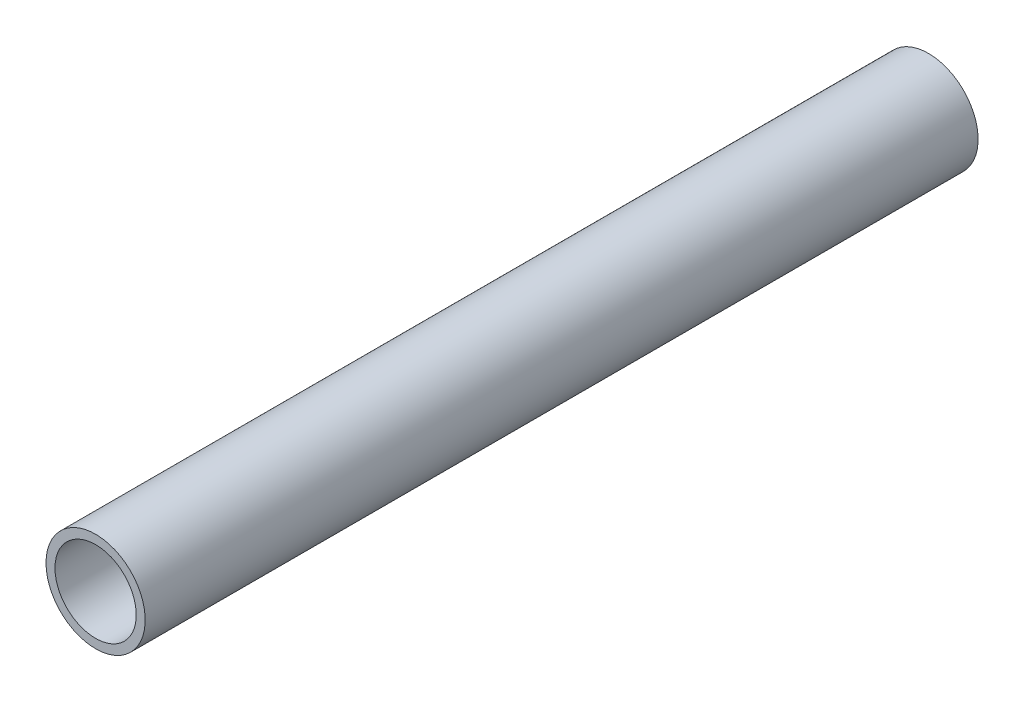
SolidWorks part; units mm, degrees
ref_plane "Front Plane" through (0, 0, 0) normal (0, 0, 1) x (1, 0, 0)
ref_plane "Top Plane" through (0, 0, 0) normal (0, 1, 0) x (1, 0, 0)
ref_plane "Right Plane" through (0, 0, 0) normal (1, 0, 0) x (0, 0, -1)
sketch "Sketch2" plane through (0, 0, 0) normal (0, 0, 1) x (1, 0, 0)
  circle A0 centre (0, 0) radius 17.272
  circle A1 centre (0, 0) radius 21.082
  dimension "D1" = 34.544
  dimension "D2" = 42.164
extrude "Boss-Extrude1" add sketch "Sketch2" along normal blind 354.0125 contours A1 A0 region at (-20.4857, 0, 0)
